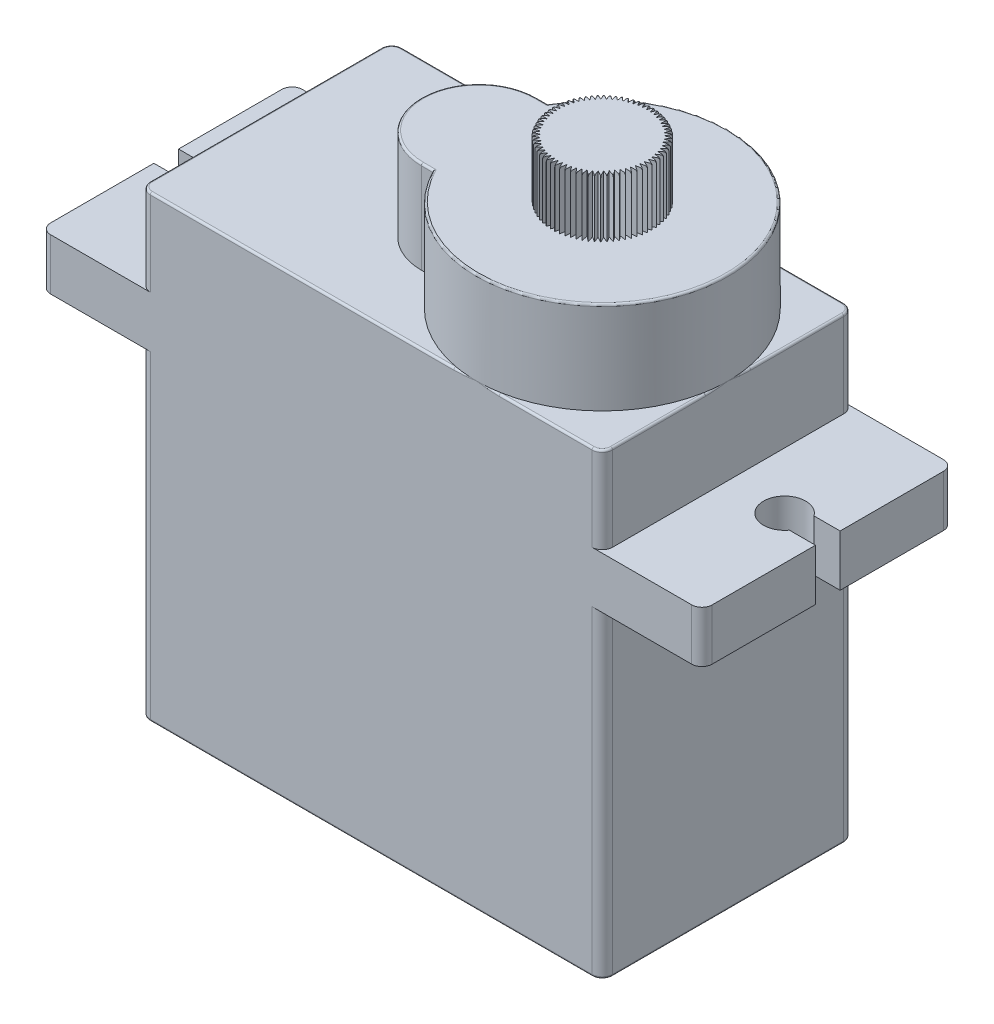
SolidWorks part; units mm, degrees
material "Q235"
ref_plane "前视" through (0, 0, 0) normal (0, 0, 1) x (1, 0, 0)
ref_plane "上视" through (0, 0, 0) normal (0, 1, 0) x (1, 0, 0)
ref_plane "右视" through (0, 0, 0) normal (1, 0, 0) x (0, 0, -1)
sketch "草图1" plane through (0, 0, 0) normal (0, 1, 0) x (1, 0, 0)
  line L1 (-11.25, 6.125) -> (11.25, 6.125)
  line L2 (-11.25, 6.125) -> (-11.25, -6.125)
  line L3 (-11.25, -6.125) -> (11.25, -6.125)
  line L4 (11.25, 6.125) -> (11.25, -6.125)
  line L5 (-11.25, 6.125) -> (11.25, -6.125) construction
  line L6 (-11.25, -6.125) -> (11.25, 6.125) construction
  point P0 (0, 0)
  dimension "D1" = 22.5
  dimension "D2" = 12.25
extrude "凸台-拉伸1" add sketch "草图1" along normal blind 15.6
sketch "草图2" plane through (0, 15.6, 0) normal (0, 1, 0) x (1, 0, 0)
  line L0 (0, 0) -> (20.5991, 0) construction
  line L1 (0, 0) -> (0, 10.7993) construction
  line L2 (11.25, 6.125) -> (16.1, 6.125)
  line L3 (16.1, 6.125) -> (16.1, 0.6)
  line L4 (11.25, -6.125) -> (11.25, 6.125)
  line L5 (11.25, 6.125) -> (-11.25, 6.125)
  line L6 (-11.25, 6.125) -> (-11.25, -6.125)
  line L7 (-11.25, -6.125) -> (11.25, -6.125)
  line L8 (-16.1, -0.6) -> (-14.831, -0.6)
  line L9 (11.25, 6.125) -> (-11.25, 6.125)
  line L10 (-16.1, 0.6) -> (-14.831, 0.6)
  line L11 (-11.25, -6.125) -> (11.25, -6.125)
  line L12 (16.1, -6.125) -> (11.25, -6.125)
  line L13 (16.1, 0.6) -> (14.831, 0.6)
  line L14 (16.1, -0.6) -> (14.831, -0.6)
  line L15 (16.1, -0.6) -> (16.1, -6.125)
  line L16 (-11.25, 6.125) -> (-16.1, 6.125)
  line L17 (-16.1, 6.125) -> (-16.1, 0.6)
  line L18 (-16.1, -6.125) -> (-11.25, -6.125)
  line L19 (-16.1, -0.6) -> (-16.1, -6.125)
  arc A0 (14.831, 0.6) -> (14.831, -0.6) centre (14, 0) ccw
  arc A1 (-14.831, 0.6) -> (-14.831, -0.6) centre (-14, 0) cw
  dimension "D3" = 2.05
  dimension "D2" = 4.85
  dimension "D4" = 14
  dimension "D5" = 1.2
  dimension "D6" = 1.269
  dimension "D1" = 0
extrude "凸台-拉伸2" add sketch "草图2" along normal blind 2.5
sketch "草图3" plane through (0, 18.1, 0) normal (0, 1, 0) x (1, 0, 0)
  line L4 (11.25, -6.125) -> (11.25, 6.125)
  line L5 (-11.25, -6.125) -> (11.25, -6.125)
  line L6 (-11.25, 6.125) -> (-11.25, -6.125)
  line L7 (11.25, 6.125) -> (-11.25, 6.125)
  line L8 (11.25, -6.125) -> (11.25, 6.125)
  line L9 (-11.25, -6.125) -> (11.25, -6.125)
  line L10 (-11.25, 6.125) -> (-11.25, -6.125)
  line L11 (11.25, 6.125) -> (-11.25, 6.125)
  dimension "D1" = 0
extrude "凸台-拉伸3" add sketch "草图3" along normal blind 4.2
sketch "草图4" plane through (0, 22.3, 0) normal (0, 1, 0) x (1, 0, 0)
  line L0 (11.25, -6.125) -> (11.25, 6.125) construction
  line L1 (-0.875, 2.8) -> (-0.3225, 2.8)
  line L2 (-0.875, -2.8) -> (-0.3225, -2.8)
  arc A0 (-0.3225, -2.8) -> (-0.3225, 2.8) centre (5.125, 0) ccw
  arc A1 (-0.875, 2.8) -> (-0.875, -2.8) centre (-0.875, 0) ccw
  dimension "D1" = 5.6
  dimension "D3" = 12.25
  dimension "D2" = 6
  dimension "D4" = 5.125
extrude "凸台-拉伸4" add sketch "草图4" along normal blind 4.5
sketch "草图5" plane through (0, 26.8, 0) normal (0, 1, 0) x (1, 0, 0)
  circle A0 centre (5.125, 0) radius 2.425
  dimension "D1" = 4.85
extrude "凸台-拉伸5" add sketch "草图5" along normal blind 2.8
fillet "圆角1" radius 0.5 12 edges at (11.25, 20.2, 6.125) (11.25, 20.2, -6.125) (16.1, 16.85, -6.125) (-16.1, 16.85, -6.125) (-11.25, 20.2, -6.125) (16.1, 16.85, 6.125) (-11.25, 20.2, 6.125) (-16.1, 16.85, 6.125) (-11.25, 7.8, -6.125) (11.25, 7.8, -6.125) (11.25, 7.8, 6.125) (-11.25, 7.8, 6.125)
fillet "圆角2" radius 0.1 24 edges at (11.1036, 0, -5.9786) (11.25, 0, 0) (11.1036, 0, 5.9786) (0, 0, 6.125) (-11.1036, 0, 5.9786) (-11.25, 0, 0) (-11.1036, 0, -5.9786) (7.9375, 22.3, -6.125) (11.1036, 22.3, -5.9786) (11.25, 22.3, -2.8125) (11.25, 22.3, 2.8125) (11.1036, 22.3, 5.9786) (7.9375, 22.3, 6.125) (-2.8125, 22.3, 6.125) (-11.1036, 22.3, 5.9786) (-11.25, 22.3, 0) (-11.1036, 22.3, -5.9786) (0, 0, -6.125) (-2.8125, 22.3, -6.125) (-0.5988, 26.8, -2.8) (-0.5988, 26.8, 2.8) (5.125, 29.6, 2.425) (-3.675, 26.8, 0) (11.25, 26.8, 0)
sketch "草图7" plane through (0, 29.6, 0) normal (0, 1, 0) x (1, 0, 0)
  line L0 (5.125, 0) -> (5.125, 1.3865) construction
  line L1 (4.975, 2.5351) -> (5.275, 2.5351)
  line L2 (5.275, 2.5351) -> (5.125, 2.1351)
  line L3 (5.125, 2.1351) -> (4.975, 2.5351)
  line L4 (5.125, 0) -> (4.1279, 0) construction
  dimension "D2" = 0.4
  dimension "D3" = 0.7485
  dimension "D1" = 0.3
extrude "切除-拉伸1" cut sketch "草图7" against normal up to surface (2.8 mm away)
pattern_circular "阵列(圆周)3" count 70 over 360 about axis through (5.125, 0, 0) along (0, 1, 0) of "切除-拉伸1"
